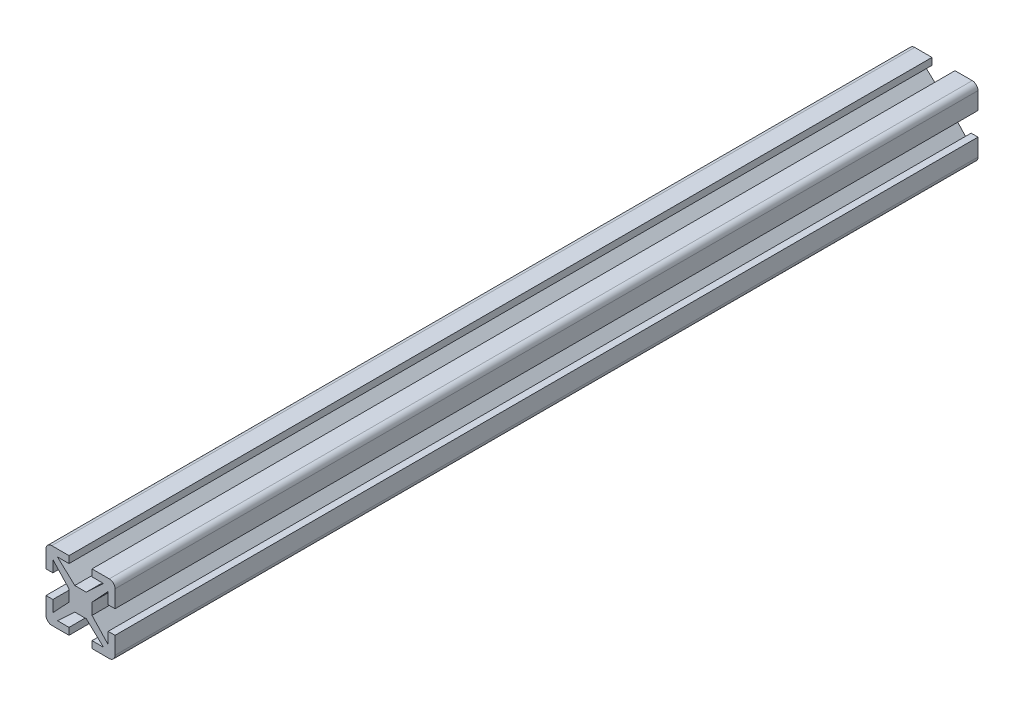
SolidWorks part; units mm, degrees
ref_plane "Plan de face" through (0, 0, 0) normal (0, 0, 1) x (1, 0, 0)
ref_plane "Plan de dessus" through (0, 0, 0) normal (0, 1, 0) x (1, 0, 0)
ref_plane "Plan de droite" through (0, 0, 0) normal (1, 0, 0) x (0, 0, -1)
sketch "Esquisse1" plane through (0, 0, 0) normal (0, 0, 1) x (1, 0, 0)
  line L0 (-6, 5) -> (-6, -5)
  line L1 (-5, 6) -> (5, 6)
  line L2 (-5, -6) -> (5, -6)
  line L3 (6, 5) -> (6, -5)
  line L4 (-5, 5) -> (5, -5) construction
  line L5 (5, 5) -> (-5, -5) construction
  arc A0 (-5, 6) -> (-6, 5) centre (-5, 5) ccw
  arc A1 (5, 6) -> (6, 5) centre (5, 5) cw
  arc A2 (6, -5) -> (5, -6) centre (5, -5) cw
  arc A3 (-5, -6) -> (-6, -5) centre (-5, -5) cw
  point P12 (0, 0)
  dimension "D1" = 1
  dimension "D2" = 1
  dimension "D4" = 1
  dimension "D3" = 12
extrude "Extrusion1" add sketch "Esquisse1" along normal mid plane 150
sketch "Esquisse3" plane through (0, 0, 75) normal (0, 0, 1) x (1, 0, 0)
  line L0 (6, 2) -> (4.8, 2)
  line L2 (4.8, 2) -> (4.8, 4)
  line L3 (2, 1) -> (2, -1)
  line L4 (4.8, -4) -> (4.8, -2)
  line L5 (4.8, -2) -> (6, -2)
  line L6 (6, -5) -> (6, 5) construction
  line L7 (4.8, 4) -> (2, 1)
  line L8 (6, 2) -> (6, -2)
  line L9 (4.8, -4) -> (2, -1)
  point P4 (6, 0)
  point P10 (6, 0)
  dimension "D1" = 4
  dimension "D2" = 1.2
  dimension "D3" = 4
  dimension "D4" = 2
  dimension "D5" = 2
extrude "Enlèv. mat.-Extru.1" cut sketch "Esquisse3" against normal through all
ref_axis "Axe1" through (0, 0, -1) along (0, 0, 1)
pattern_circular "Répétition circulaire1" count 4 every 90 about axis through (0, 0, -1) along (0, 0, 1) of "Enlèv. mat.-Extru.1"
